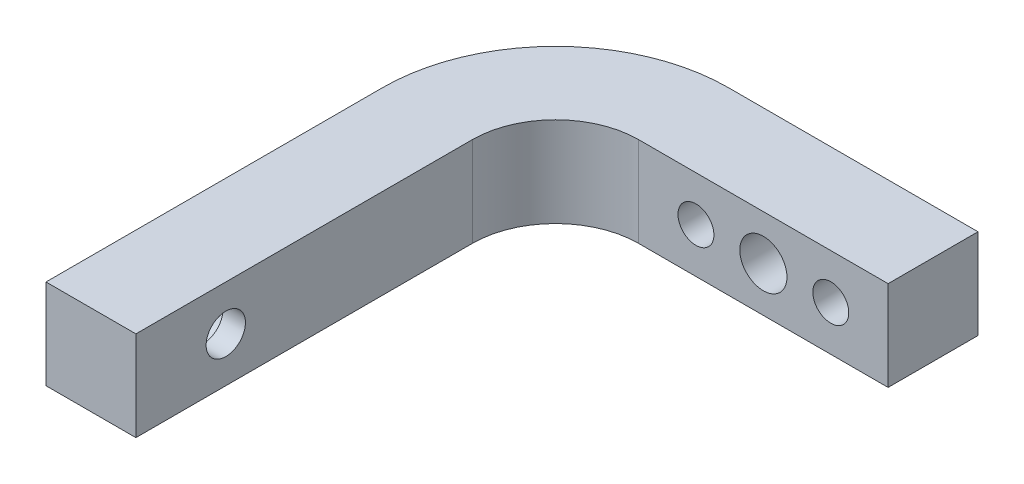
SolidWorks part; units mm, degrees
ref_plane "Front Plane" through (0, 0, 0) normal (0, 0, 1) x (1, 0, 0)
ref_plane "Top Plane" through (0, 0, 0) normal (0, 1, 0) x (1, 0, 0)
ref_plane "Right Plane" through (0, 0, 0) normal (1, 0, 0) x (0, 0, -1)
ref_axis "Z" through (0, 0, -2.267) along (0, 0, 1)
sketch "Sketch1" plane through (0, 0, 0) normal (0, 1, 0) x (1, 0, 0)
  line L0 (-11.1, 0) -> (11.1, 0)
  line L1 (-26.5, -15.4) -> (-26.5, -45.34)
  line L2 (-26.5, -45.34) -> (-18.5, -45.34)
  line L3 (-18.5, -45.34) -> (-18.5, -15.4)
  line L4 (-11.1, -8) -> (11.1, -8)
  line L5 (0, -8) -> (0, 0) construction
  line L6 (18.5, -45.34) -> (18.5, -15.4) construction
  line L7 (26.5, -45.34) -> (18.5, -45.34) construction
  line L8 (26.5, -15.4) -> (26.5, -45.34) construction
  line L9 (11.1, 0) -> (11.1, -8)
  arc A0 (-11.1, 0) -> (-26.5, -15.4) centre (-11.1, -15.4) ccw
  arc A1 (-18.5, -15.4) -> (-11.1, -8) centre (-11.1, -15.4) cw
  arc A2 (18.5, -15.4) -> (11.1, -8) centre (11.1, -15.4) ccw construction
  arc A3 (11.1, 0) -> (26.5, -15.4) centre (11.1, -15.4) cw construction
  dimension "D3" = 7.4
  dimension "D1" = 37
  dimension "D2" = 8
  dimension "D4" = 37.34
extrude "Boss-Extrude1" add sketch "Sketch1" along normal blind 4 and the other way blind 4
sketch "Sketch2" plane through (-18.5, 0, 0) normal (-1, 0, 0) x (0, 0, 1)
  line L1 (20.68, 0) -> (-20.68, 0) construction
  line L2 (0, -4.4) -> (0, 4.4) construction
  circle A0 centre (37.34, 0) radius 1.75
  dimension "D1" = 3.5
  dimension "D2" = 37.34
extrude "Cut-Extrude1" cut sketch "Sketch2" against normal through all both and the other way through all
ref_axis "Axis2" through (-60.1767, 0, 37.34) along (1, 0, 0)
sketch "Sketch3" plane through (0, 0, 0) normal (0, 0, -1) x (-1, 0, 0)
  line L0 (-6, 0) -> (6, 0) construction
  circle A0 centre (0, 0) radius 2.1
  circle A1 centre (-6, 0) radius 1.6
  circle A2 centre (6, 0) radius 1.6
  dimension "D1" = 4.2
  dimension "D3" = 3.2
  dimension "D2" = 12
extrude "Cut-Extrude2" cut sketch "Sketch3" against normal through all
sketch "Sketch4" plane through (-26.5, 0, 0) normal (1, 0, 0) x (0, 0, -1)
  circle A0 centre (-37.34, 0) radius 2.25
  circle A1 centre (-37.34, 0) radius 1.75 construction
  dimension "D1" = 4.5
extrude "Cut-Extrude3" cut sketch "Sketch4" along normal blind 6
sketch "Sketch5" plane through (-26.5, 0, 0) normal (-1, 0, 0) x (0, 0, 1)
  circle A0 centre (37.34, 0) radius 3.75
  point P2 (0, 0)
  dimension "D1" = 7.5
extrude "Cut-Extrude4" cut sketch "Sketch5" against normal blind 0.75
equation "\"width\"= \"EyeDiameter\" + \"EyeClearance\""
equation "\"prongwidth\"= 8"
equation "\"D2@Sketch1\"=\"prongwidth\""
equation "\"D3@Sketch1\"=\"width\"/5"
equation "\"pronglength\"= \"BasePlaneDistance\"'model implicitly adds clearance (of prongwidth) to the hole drilled at the baseplanedistance"
equation "\"D4@Sketch1\"=\"pronglength\""
equation "\"D1@Boss-Extrude1\"=\"prongwidth\"/2"
equation "\"D2@Boss-Extrude1\"=\"prongwidth\"/2"
equation "\"lbracket-plane-to-axis\"= \"BasePlaneDistance\""
equation "\"D2@Sketch2\"=\"lbracket-plane-to-axis\""
equation "\"EyeDiameter\" = 35"
equation "\"BasePlaneDistance\" = \"EyeDiameter\"/2+19.84"
equation "\"EyeClearance\" = 2"
equation "\"D1@Sketch1\"=\"EyeDiameter\"+\"EyeClearance\""
equation "\"BearingDepth\"= 6"
equation "\"BearingHousingID\"= 4.5"
equation "\"D1@Sketch4\"=\"BearingHousingID\""
equation "\"D1@Cut-Extrude3\"=\"BearingDepth\""
equation "\"BearingFlangeThickness\"= 0.75"
equation "\"BearingFlangeOD\"= 7.5"
equation "\"D1@Sketch5\"=\"BearingFlangeOD\""
equation "\"D1@Cut-Extrude4\"=\"BearingFlangeThickness\""
